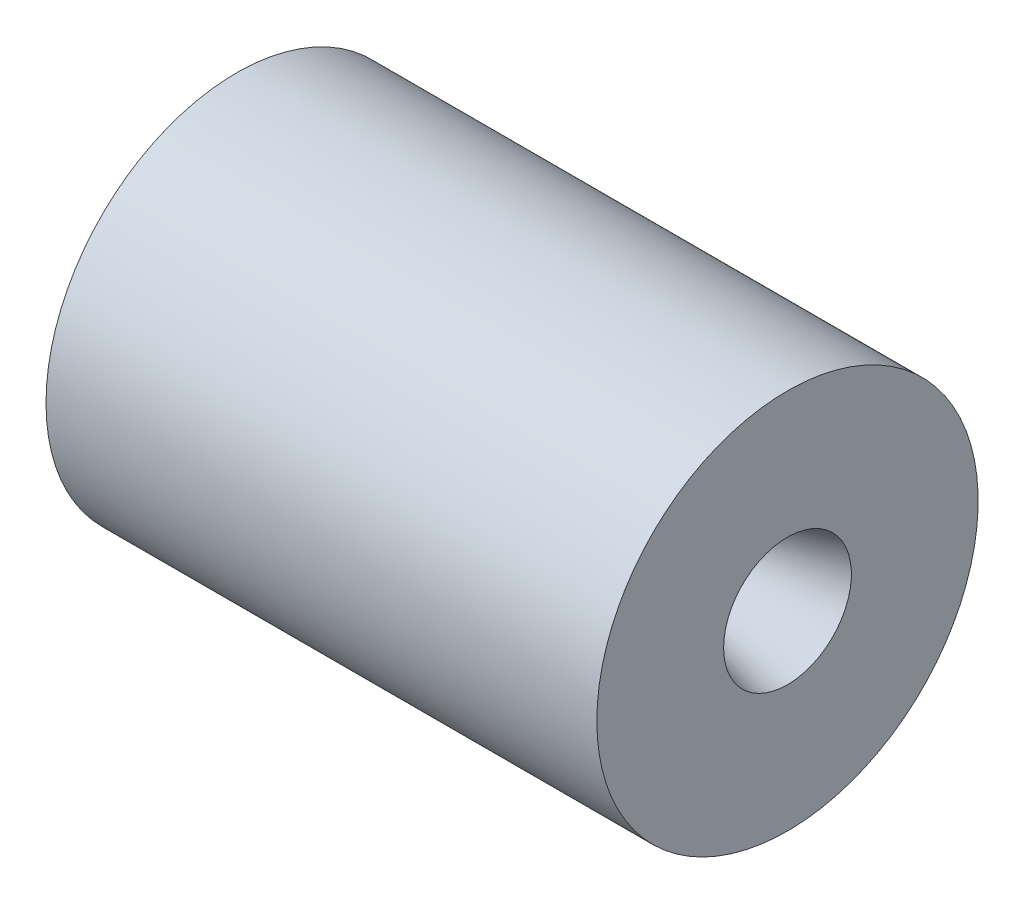
SolidWorks part; units mm, degrees
material "S-Glass Fiber"
ref_plane "Front Plane" through (0, 0, 0) normal (0, 0, 1) x (1, 0, 0)
ref_plane "Top Plane" through (0, 0, 0) normal (0, 1, 0) x (1, 0, 0)
ref_plane "Right Plane" through (0, 0, 0) normal (1, 0, 0) x (0, 0, -1)
sketch "Sketch1" plane through (0, 0, 0) normal (0, 0, 1) x (1, 0, 0)
  line L0 (-50.8993, 0) -> (36.1756, 0) construction
  line L1 (-51.622, 22.225) -> (-18.0499, 22.225)
  line L2 (-11.406, 18.5053) -> (-3.2526, 5.207)
  line L3 (0.8218, 3.4544) -> (18.1648, 8.0954)
  line L4 (0, 0) -> (0, 3.3528) construction
  line L5 (-51.622, 22.225) -> (-51.622, 24.1554)
  line L6 (-51.622, 24.1554) -> (18.1648, 24.1554)
  line L7 (18.1648, 24.1554) -> (18.1648, 8.0954)
  arc A0 (-18.0499, 22.225) -> (-11.406, 18.5053) centre (-18.0499, 14.4318) cw
  arc A1 (-3.2526, 5.207) -> (0, 3.3528) centre (0.06, 7.238) ccw
  arc A2 (0, 3.3528) -> (0.8218, 3.4544) centre (0.0463, 6.352) ccw
  dimension "D1" = 22.225
  dimension "D2" = 51.622
  dimension "D3" = 18.5053
  dimension "D4" = 3.3528
  dimension "D5" = 5.207
  dimension "D6" = 11.406
  dimension "D7" = 0.8218
  dimension "D8" = 18.1648
  dimension "D9" = 8.0954
  dimension "D10" = 3.4544
  dimension "D11" = 48.3108
revolve "Revolve1" add sketch "Sketch1" angle 360 about L0
equation "\"inj_x\"= 2.0323615201475906"
equation "\"inj_y\"= 0.875"
equation "\"b_x\"= 1.0541546713311643"
equation "\"b_y\"= 0.875"
equation "\"c_x\"= 0.7006012807378904"
equation "\"c_y\"= 0.7285533905932737"
equation "\"d_x\"= 0.1767766952966369"
equation "\"d_y\"= 0.20472880515202027"
equation "\"o_x\"= 0.0"
equation "\"o_y\"= 0.13150550044865716"
equation "\"n_x\"= 0.03235238063781509"
equation "\"n_y\"= 0.13576394800628575"
equation "\"e_x\"= 0.7151478445997492"
equation "\"e_y\"= 0.31871844117051973"
equation "\"D1@Sketch1\"=\"inj_y\""
equation "\"D2@Sketch1\"=\"inj_x\""
equation "\"D3@Sketch1\"=\"c_y\""
equation "\"D7@Sketch1\"=\"n_x\""
equation "\"D8@Sketch1\"=\"e_x\""
equation "\"D9@Sketch1\"=\"e_y\""
